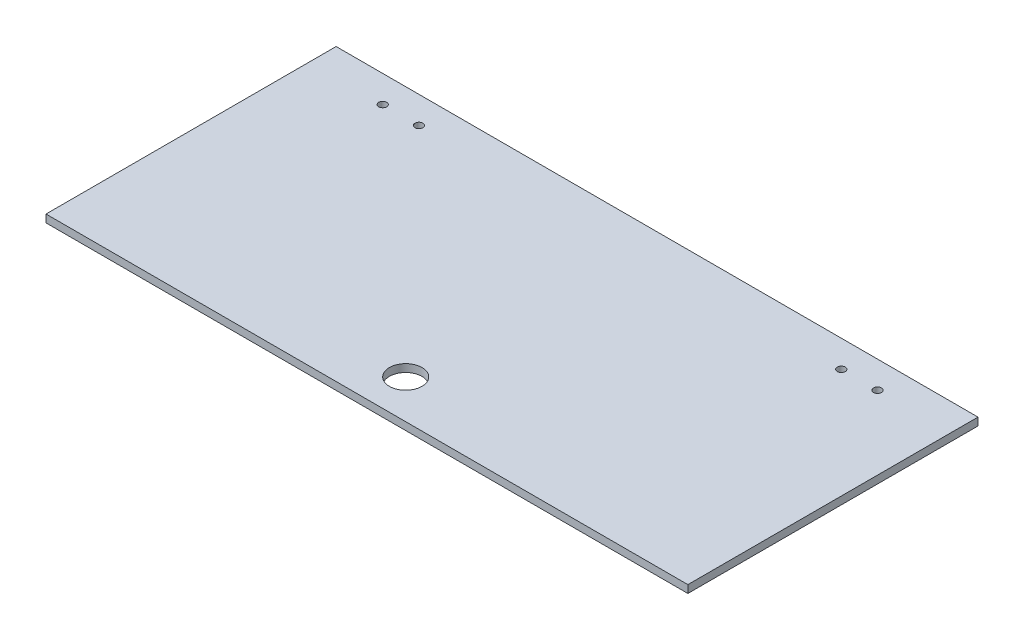
SolidWorks part; units mm, degrees
ref_plane "Front Plane" through (0, 0, 0) normal (0, 0, 1) x (1, 0, 0)
ref_plane "Top Plane" through (0, 0, 0) normal (0, 1, 0) x (1, 0, 0)
ref_plane "Right Plane" through (0, 0, 0) normal (1, 0, 0) x (0, 0, -1)
sketch "Sketch1" plane through (0, 0, 0) normal (0, 1, 0) x (1, 0, 0)
  line L0 (125, 113) -> (125, 0) construction
  line L1 (0, 113) -> (250, 113)
  line L2 (0, 113) -> (0, 0)
  line L3 (0, 0) -> (250, 0)
  line L4 (250, 113) -> (250, 0)
  circle A0 centre (28.65, 102.5) radius 1.55
  circle A1 centre (42.75, 102.5) radius 1.55
  circle A2 centre (207.25, 102.5) radius 1.55
  circle A3 centre (221.35, 102.5) radius 1.55
  circle A4 centre (125, 15.1) radius 6.35
  dimension "D2" = 3.1
  dimension "D7" = 12.7
  dimension "D8" = 15.1
  dimension "D1" = 250
  dimension "D3" = 14.1
  dimension "D4" = 28.65
  dimension "D5" = 10.5
  dimension "D6" = 113
extrude "Boss-Extrude1" add sketch "Sketch1" along normal blind 3
equation "\"cf_tube_outer_diameter\"= 25mm"
equation "\"cf_tube_inner_diameter\" = 21mm"
equation "\"mid_plate_mid_to_top\" = 100mm"
equation "\"mid_plate_mid_to_bottom\" = 30mm"
equation "\"mid_plate_horizontal_spacing\"=250mm"
equation "\"cf_plate_thickness\" =4mm"
equation "\"mid_tube_length\" = 121mm"
equation "\"mid_plate_bottom_width\" = 180mm"
equation "\"mid_support_plate_distance\" = 250mm"
equation "\"nut_strip_2_hole_distance\" = 7mm"
equation "\"nut_strip_hole_diameter\" = 2.5mm"
equation "\"nut_strip_hole_to_edge_distance\"= 2.5mm"
